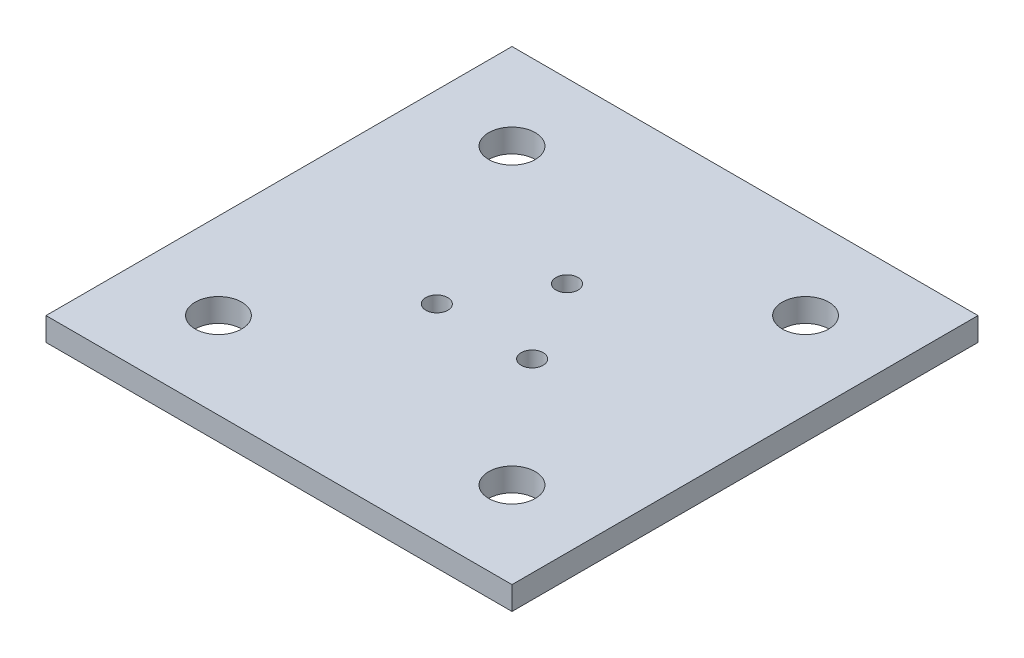
SolidWorks part; units mm, degrees
ref_plane "Front Plane" through (0, 0, 0) normal (0, 0, 1) x (1, 0, 0)
ref_plane "Top Plane" through (0, 0, 0) normal (0, 1, 0) x (1, 0, 0)
ref_plane "Right Plane" through (0, 0, 0) normal (1, 0, 0) x (0, 0, -1)
sketch "Sketch1" plane through (0, 0, 0) normal (0, 1, 0) x (1, 0, 0)
  line L1 (-31.75, -31.75) -> (31.75, -31.75)
  line L2 (-31.75, -31.75) -> (-31.75, 31.75)
  line L3 (-31.75, 31.75) -> (31.75, 31.75)
  line L4 (31.75, -31.75) -> (31.75, 31.75)
  line L5 (-31.75, -31.75) -> (31.75, 31.75) construction
  line L6 (-31.75, 31.75) -> (31.75, -31.75) construction
  circle A0 centre (0, 0) radius 19.05 construction
  dimension "D1" = 38.1
  dimension "D2" = 63.5
  dimension "D3" = 63.5
extrude "Boss-Extrude1" add sketch "Sketch1" along normal blind 3.175
sketch "Sketch2" plane through (0, 3.175, 0) normal (0, 1, 0) x (1, 0, 0)
  circle A0 centre (0, 0) radius 7.5 construction
  circle A1 centre (0, 7.5) radius 1.5
  circle A2 centre (6.4952, -3.75) radius 1.5
  circle A3 centre (-6.4952, -3.75) radius 1.5
  point P11 (0, 0)
  dimension "D2" = 15
  dimension "D3" = 3
  dimension "D1" = 3
extrude "Cut-Extrude1" cut sketch "Sketch2" against normal through all contours A1 | A3 | A2
sketch "Sketch3" plane through (0, 3.175, 0) normal (0, 1, 0) x (1, 0, 0)
  line L1 (-20, -20) -> (20, -20) construction
  line L2 (-20, -20) -> (-20, 20) construction
  line L3 (-20, 20) -> (20, 20) construction
  line L4 (20, -20) -> (20, 20) construction
  line L5 (-20, -20) -> (20, 20) construction
  line L6 (-20, 20) -> (20, -20) construction
  circle A0 centre (-20, 20) radius 3.175
  circle A1 centre (20, 20) radius 3.175
  circle A2 centre (20, -20) radius 3.175
  circle A3 centre (-20, -20) radius 3.175
  point P0 (0, 0)
  point P4 (0, 0)
  point P7 (14.0269, -10.9807)
  dimension "D3" = 6.35
  dimension "D1" = 40
  dimension "D2" = 40
  dimension "D4" = 2
  dimension "D5" = 2
extrude "Cut-Extrude2" cut sketch "Sketch3" against normal through all contours A0 | A3 | A2 | A1 region at (-20, 3.175, -20) region at (20, 3.175, -20) region at (20, 3.175, 20) region at (-20, 3.175, 20)
